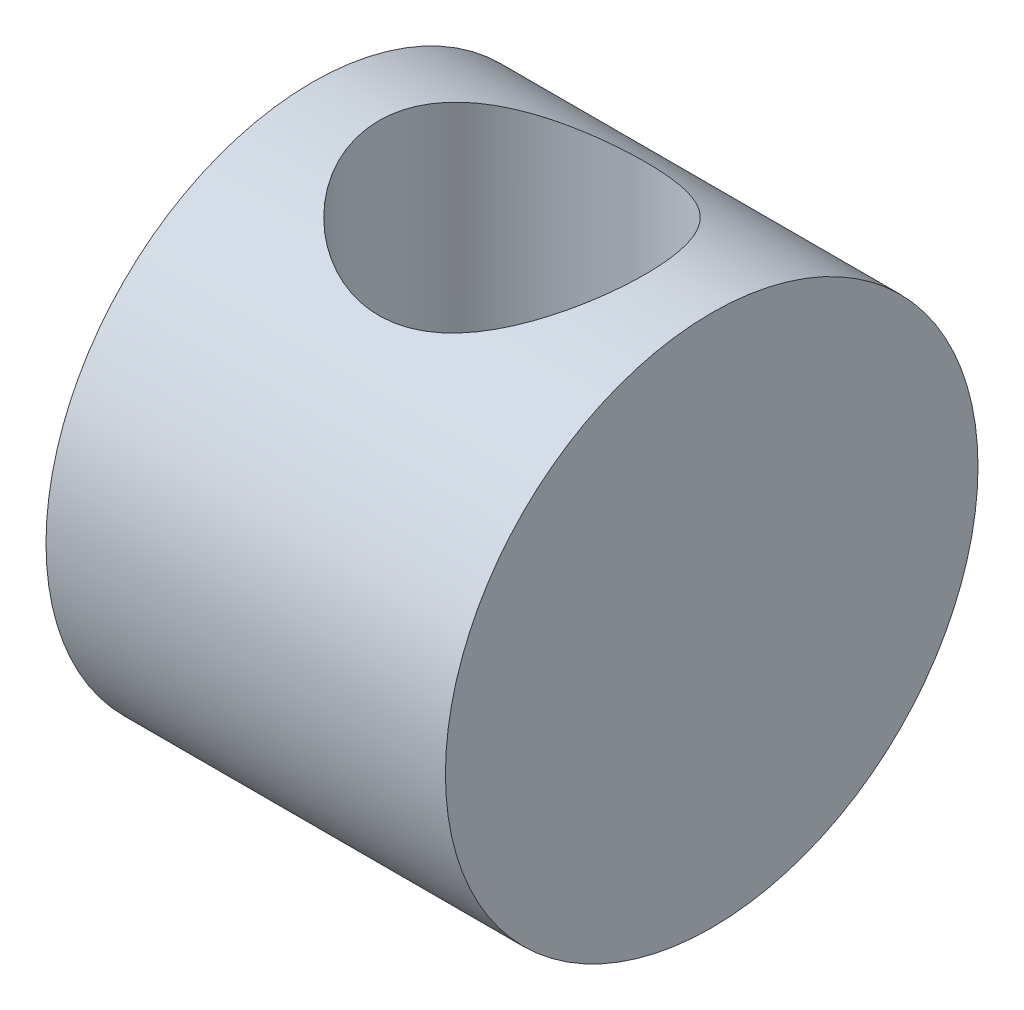
SolidWorks part; units mm, degrees
ref_plane "Front Plane" through (0, 0, 0) normal (0, 0, 1) x (1, 0, 0)
ref_plane "Top Plane" through (0, 0, 0) normal (0, 1, 0) x (1, 0, 0)
ref_plane "Right Plane" through (0, 0, 0) normal (1, 0, 0) x (0, 0, -1)
sketch "Sketch1" plane through (0, 0, 0) normal (1, 0, 0) x (0, 0, -1)
  circle A0 centre (0, 0) radius 50
  dimension "D1" = 100
extrude "Boss-Extrude1" add sketch "Sketch1" along normal blind 75
sketch "Sketch2" plane through (0, 0, 0) normal (0, 1, 0) x (1, 0, 0)
  circle A0 centre (37.5, 0) radius 25
  dimension "D1" = 50
extrude "Cut-Extrude1" cut sketch "Sketch2" against normal blind 100 and the other way blind 100
